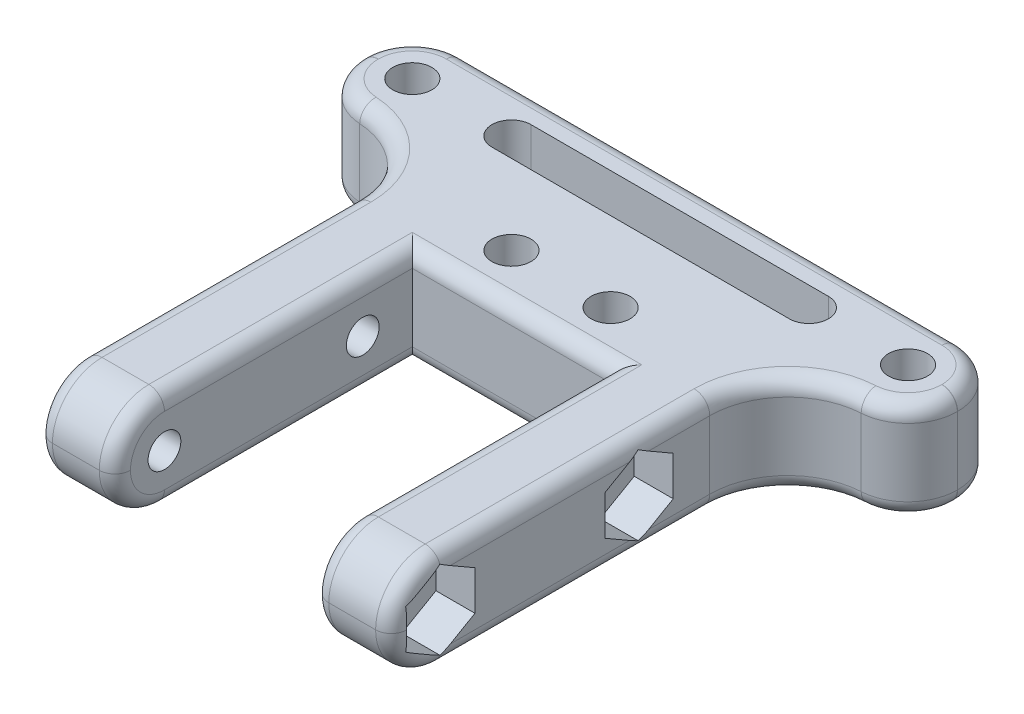
SolidWorks part; units mm, degrees
ref_plane "Front Plane" through (0, 0, 0) normal (0, 0, 1) x (1, 0, 0)
ref_plane "Top Plane" through (0, 0, 0) normal (0, 1, 0) x (1, 0, 0)
ref_plane "Right Plane" through (0, 0, 0) normal (1, 0, 0) x (0, 0, -1)
sketch "Sketch1" plane through (0, 0, 0) normal (0, 1, 0) x (1, 0, 0)
  line L0 (31.75, -6.35) -> (31.75, -37.8692) construction
  line L1 (-6.35, 6.35) -> (69.85, 6.35)
  line L2 (-6.35, 6.35) -> (-6.35, -6.35)
  line L3 (-6.35, -6.35) -> (-0.95, -6.35)
  line L4 (69.85, 6.35) -> (69.85, -6.35)
  line L6 (9.05, -16.35) -> (9.05, -57.15)
  line L7 (9.05, -57.15) -> (19.05, -57.15)
  line L11 (44.45, -57.15) -> (54.45, -57.15)
  line L12 (54.45, -16.35) -> (54.45, -57.15)
  line L13 (64.45, -6.35) -> (69.85, -6.35)
  line L14 (19.05, -57.15) -> (19.05, -19.05)
  line L15 (19.05, -19.05) -> (44.45, -19.05)
  line L16 (44.45, -19.05) -> (44.45, -57.15)
  line L17 (12.7, 0) -> (50.8, 0) construction
  line L18 (12.7, 2.5) -> (50.8, 2.5)
  line L19 (12.7, -2.5) -> (50.8, -2.5)
  circle A0 centre (0, 0) radius 2.5
  circle A1 centre (63.5, 0) radius 2.5
  arc A2 (9.05, -16.35) -> (-0.95, -6.35) centre (-0.95, -16.35) ccw
  arc A3 (54.45, -16.35) -> (64.45, -6.35) centre (64.45, -16.35) cw
  arc A4 (12.7, 2.5) -> (12.7, -2.5) centre (12.7, 0) ccw
  arc A5 (50.8, -2.5) -> (50.8, 2.5) centre (50.8, 0) ccw
  circle A6 centre (38.1, -12.7) radius 2.5
  circle A7 centre (25.4, -12.7) radius 2.5
  point P23 (54.45, -6.35)
  point P26 (31.75, 0)
  point P35 (0, 0)
  dimension "D1" = 5
  dimension "D10" = 10
  dimension "D16" = 2.5
  dimension "D2" = 63.5
  dimension "D3" = 6.35
  dimension "D4" = 6.35
  dimension "D5" = 12.7
  dimension "D6" = 6.35
  dimension "D7" = 25.4
  dimension "D8" = 10
  dimension "D9" = 10
  dimension "D11" = 50.8
  dimension "D13" = 6.35
  dimension "D14" = 50.8
  dimension "D15" = 38.1
  dimension "D17" = 12.7
  dimension "D18" = 12.7
  dimension "D19" = 6.35
extrude "Boss-Extrude2" add sketch "Sketch1" along normal blind 12.7
fillet "Fillet1" radius 6.35 4 edges at (49.45, 0, 57.15) (49.45, 12.7, 57.15) (14.05, 0, 57.15) (14.05, 12.7, 57.15)
fillet "Fillet2" radius 6.35 4 edges at (69.85, 6.35, 6.35) (69.85, 6.35, -6.35) (-6.35, 6.35, -6.35) (-6.35, 6.35, 6.35)
fillet "Fillet3" radius 2 26 edges at (-4.6187, 12.7, 4.3854) (-6.35, 12.7, 0.0138) (-4.4901, 12.7, -4.4901) (31.75, 12.7, -6.35) (67.9901, 12.7, -4.4901) (69.85, 12.7, 0.0138) (68.1187, 12.7, 4.3854) (57.1764, 12.7, 9.4874) (54.45, 12.7, 33.575) (54.45, 10.8401, 55.2901) (54.45, 1.8599, 55.2901) (54.45, 0, 33.575) (57.1764, 0, 9.4874) (68.1187, 0, 4.3854) (69.85, 0, 0.0138) (67.9901, 0, -4.4901) (31.75, 0, -6.35) (-4.4901, 0, -4.4901) (-6.35, 0, 0.0138) (-4.6187, 0, 4.3854) (6.3236, 0, 9.4874) (9.05, 0, 33.575) (9.05, 1.8599, 55.2901) (9.05, 10.8401, 55.2901) (9.05, 12.7, 33.575) (6.3236, 12.7, 9.4874)
sketch "Sketch2" plane through (9.05, 0, 0) normal (-1, 0, 0) x (0, 0, 1)
  line L0 (50.8, 10.7) -> (50.8, 12.7) construction
  line L1 (55.15, 6.35) -> (57.15, 6.35) construction
  circle A0 centre (50.8, 6.35) radius 2.1
  circle A1 centre (25.4, 6.35) radius 2.1
  circle A2 centre (25.4, 6.35) radius 4.25
  point P7 (50.8, 11.7)
  dimension "D1" = 4.2
  dimension "D2" = 4.2
  dimension "D4" = 8.5
  dimension "D3" = 25.4
extrude "Cut-Extrude1" cut sketch "Sketch2" against normal up to surface (45.4 mm away) contours A0 | A1 region at (9.05, 6.35, 50.8) region at (9.05, 6.35, 25.4) up to face at (54.45, 6.35, 38.2504)
sketch "Sketch3" plane through (54.45, 0, 0) normal (1, 0, 0) x (0, 0, -1)
  line L1 (-25.4, 1.2982) -> (-21.025, 3.8241)
  line L2 (-21.025, 3.8241) -> (-21.025, 8.8759)
  line L3 (-21.025, 8.8759) -> (-25.4, 11.4018)
  line L4 (-25.4, 11.4018) -> (-29.775, 8.8759)
  line L5 (-29.775, 8.8759) -> (-29.775, 3.8241)
  line L6 (-29.775, 3.8241) -> (-25.4, 1.2982)
  line L7 (-50.8, 1.2982) -> (-46.425, 3.8241)
  line L8 (-46.425, 3.8241) -> (-46.425, 8.8759)
  line L9 (-46.425, 8.8759) -> (-50.8, 11.4018)
  line L10 (-50.8, 11.4018) -> (-55.175, 8.8759)
  line L11 (-55.175, 8.8759) -> (-55.175, 3.8241)
  line L12 (-55.175, 3.8241) -> (-50.8, 1.2982)
  circle A0 centre (-25.4, 6.35) radius 4.375 construction
  circle A1 centre (-50.8, 6.35) radius 4.375 construction
  dimension "D1" = 8.75
  dimension "D2" = 8.75
extrude "Cut-Extrude4" cut sketch "Sketch3" against normal blind 5 and the other way blind 12.7
fillet "Fillet4" radius 2 10 edges at (19.05, 0, 34.925) (19.05, 1.8599, 55.2901) (19.05, 10.8401, 55.2901) (44.45, 0, 34.925) (44.45, 1.8599, 55.2901) (44.45, 10.8401, 55.2901) (19.05, 12.7, 34.925) (31.75, 0, 19.05) (31.75, 12.7, 19.05) (44.45, 12.7, 34.925)
